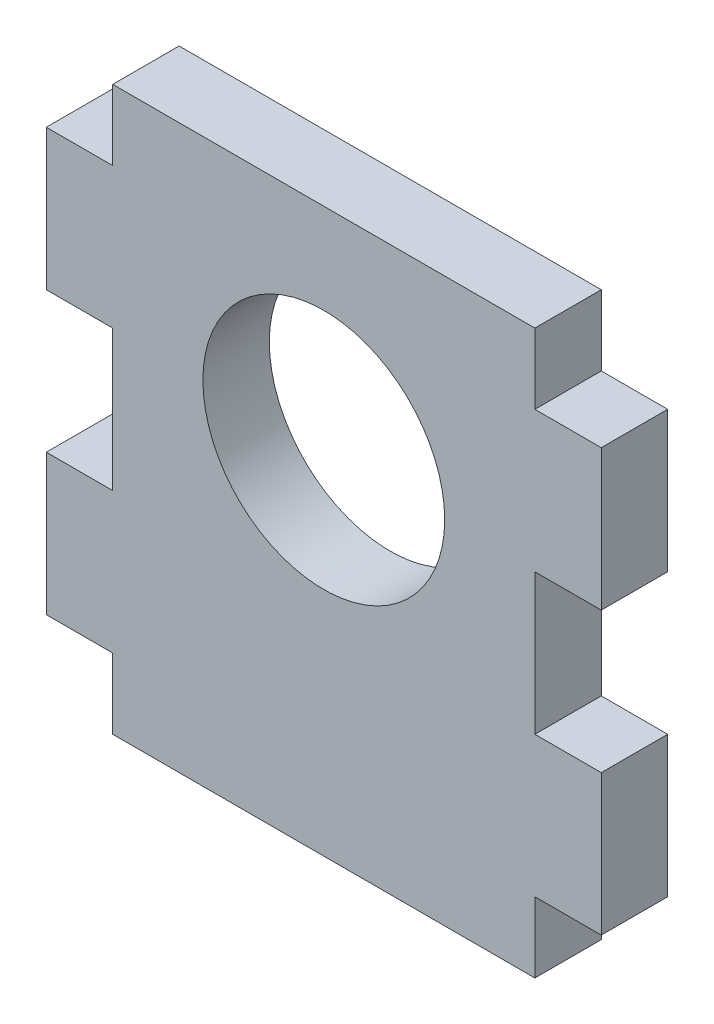
SolidWorks part; units mm, degrees
ref_plane "Front Plane" through (0, 0, 0) normal (0, 0, 1) x (1, 0, 0)
ref_plane "Top Plane" through (0, 0, 0) normal (0, 1, 0) x (1, 0, 0)
ref_plane "Right Plane" through (0, 0, 0) normal (1, 0, 0) x (0, 0, -1)
sketch "Sketch1" plane through (0, 0, 0) normal (0, 0, 1) x (1, 0, 0)
  line L0 (0, 19.05) -> (0, -31.75) construction
  line L1 (19.05, 19.05) -> (-19.05, 19.05)
  line L2 (19.05, 19.05) -> (19.05, 12.7)
  line L3 (19.05, -31.75) -> (-19.05, -31.75)
  line L4 (-19.05, 19.05) -> (-19.05, 12.7)
  line L5 (-19.05, -6.35) -> (19.05, -6.35) construction
  line L6 (-25.0444, -25.4) -> (-25.0444, -12.7)
  line L7 (-19.05, 12.7) -> (-25.0444, 12.7)
  line L8 (-19.05, -25.4) -> (-19.05, -31.75)
  line L9 (-19.05, 0) -> (-25.0444, 0)
  line L10 (-25.0444, 12.7) -> (-25.0444, 0)
  line L11 (-19.05, -12.7) -> (-25.0444, -12.7)
  line L12 (19.05, -25.4) -> (19.05, -31.75)
  line L13 (-19.05, -25.4) -> (-25.0444, -25.4)
  line L14 (19.05, -25.4) -> (25.0444, -25.4)
  line L15 (19.05, 0) -> (19.05, -12.7)
  line L16 (19.05, -12.7) -> (25.0444, -12.7)
  line L17 (25.0444, 12.7) -> (25.0444, 0)
  line L18 (19.05, 0) -> (25.0444, 0)
  line L20 (19.05, 12.7) -> (25.0444, 12.7)
  line L21 (25.0444, -25.4) -> (25.0444, -12.7)
  line L22 (-19.05, 0) -> (-19.05, -12.7)
  circle A0 centre (0, 0) radius 10.9125
  dimension "D1" = 21.825
  dimension "D2" = 19.05
  dimension "D3" = 38.1
  dimension "D4" = 50.8
  dimension "D5" = 5.9944
  dimension "D6" = 12.7
  dimension "D7" = 6.35
extrude "Boss-Extrude1" add sketch "Sketch1" along normal blind 5.9944
